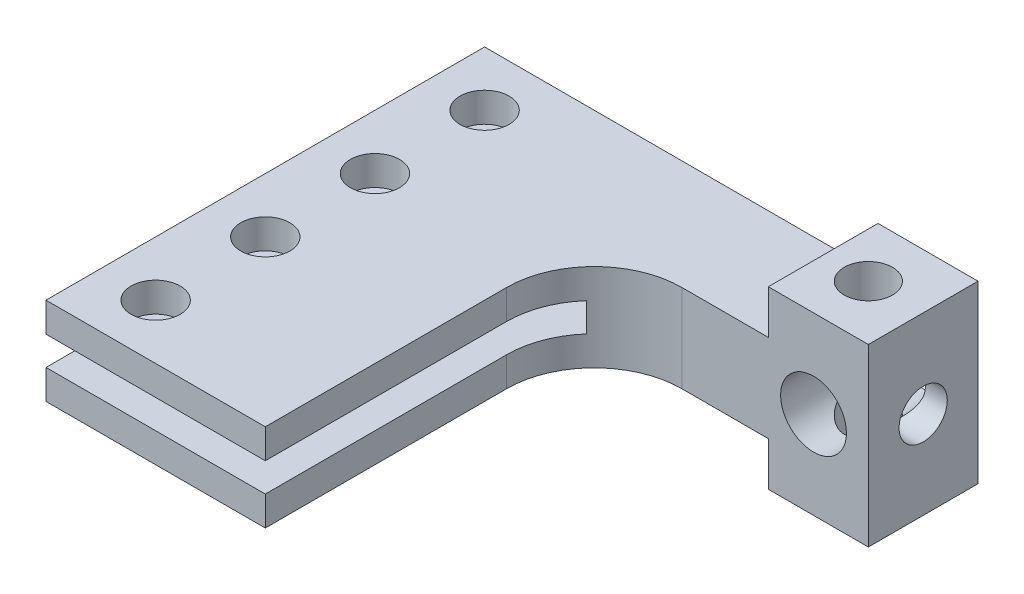
SolidWorks part; units mm, degrees
ref_plane "Front Plane" through (0, 0, 0) normal (0, 0, 1) x (1, 0, 0)
ref_plane "Top Plane" through (0, 0, 0) normal (0, 1, 0) x (1, 0, 0)
ref_plane "Right Plane" through (0, 0, 0) normal (1, 0, 0) x (0, 0, -1)
sketch "Sketch1" plane through (0, 0, 0) normal (0, 1, 0) x (1, 0, 0)
  line L0 (-33.097, 5.3879) -> (-20.397, 5.3879)
  line L2 (-20.397, 5.3879) -> (-4.522, 5.3879)
  line L3 (-4.522, 5.3879) -> (-4.522, -0.9621)
  line L4 (-4.522, -0.9621) -> (-20.397, -0.9621)
  line L5 (-20.397, -0.9621) -> (-20.397, -20.0121)
  line L6 (-20.397, -20.0121) -> (-33.097, -20.0121)
  line L7 (-33.097, -20.0121) -> (-33.097, 5.3879)
  dimension "D1" = 25.4
  dimension "D2" = 12.7
  dimension "D3" = 6.35
  dimension "D4" = 15.875
extrude "Boss-Extrude1" add sketch "Sketch1" along normal blind 5.08
sketch "Sketch2" plane through (-33.097, 0, 0) normal (-1, 0, 0) x (0, 0, 1)
  line L0 (-5.3879, 5.08) -> (-5.3879, 0) construction
  line L1 (-5.3879, 3.3735) -> (20.0121, 3.3735)
  line L2 (-5.3879, 3.3735) -> (-5.3879, 1.7065)
  line L3 (-5.3879, 1.7065) -> (20.0121, 1.7065)
  line L4 (20.0121, 3.3735) -> (20.0121, 1.7065)
  line L5 (20.0121, 5.08) -> (20.0121, 0) construction
  line L6 (7.3121, 5.08) -> (7.3121, 3.3735) construction
  line L7 (-5.3879, 5.08) -> (20.0121, 5.08) construction
  line L8 (7.3121, 1.7065) -> (7.3121, 0) construction
  line L9 (-5.3879, 0) -> (20.0121, 0) construction
  dimension "D1" = 1.6669
extrude "Cut-Extrude1" cut sketch "Sketch2" against normal blind 13.97
sketch "Sketch3" plane through (0, 5.08, 0) normal (0, 1, 0) x (1, 0, 0)
  line L0 (-33.097, 5.3879) -> (-33.097, -20.0121) construction
  line L2 (-33.097, -20.0121) -> (-20.397, -20.0121) construction
  circle A0 centre (-29.922, -16.8371) radius 1.4224
  circle A1 centre (-29.922, -10.4871) radius 1.4224
  circle A2 centre (-29.922, -4.1371) radius 1.4224
  circle A3 centre (-29.922, 2.2129) radius 1.4224
  dimension "D1" = 2.8448
  dimension "D4" = 4
  dimension "D2" = 3.175
  dimension "D3" = 3.175
  dimension "D5" = 6.35
extrude "Cut-Extrude2" cut sketch "Sketch3" against normal blind 12.7
sketch "Sketch8" plane through (0, 5.08, 0) normal (0, 1, 0) x (1, 0, 0)
  line L0 (-20.397, -0.9621) -> (-4.522, -0.9621) construction
  line L1 (-4.522, 5.3879) -> (-10.3146, 5.3879)
  line L2 (-4.522, 5.3879) -> (-4.522, -0.9621)
  line L3 (-4.522, -0.9621) -> (-10.3146, -0.9621)
  line L4 (-10.3146, 5.3879) -> (-10.3146, -0.9621)
extrude "Boss-Extrude2" add sketch "Sketch8" along normal blind 2.54 and the other way blind 7.62
sketch "Sketch5" plane through (0, 0, 0.9621) normal (0, 0, 1) x (1, 0, 0)
  line L2 (-9.602, 2.54) -> (-9.602, 5.4864) construction
  circle A1 centre (-7.697, 2.54) radius 1.905
  dimension "D1" = 3.81
extrude "Cut-Extrude3" cut sketch "Sketch5" against normal blind 12.7
fillet "Fillet3" radius 5.08 2 edges at (-20.397, 4.2267, 0.9621) (-20.397, 0.8533, 0.9621)
sketch "Sketch7" plane through (0, 5.08, 0) normal (0, 1, 0) x (1, 0, 0)
  line L0 (-7.697, -0.9621) -> (-7.697, 5.3879) construction
  line L2 (-10.3146, 5.3879) -> (-33.097, 5.3879) construction
  circle A0 centre (-7.697, 2.2129) radius 1.397
  dimension "D1" = 2.794
extrude "Cut-Extrude5" cut sketch "Sketch7" against normal through all and the other way through all contours A0
sketch "Sketch6" plane through (-4.522, 0, 0) normal (1, 0, 0) x (0, 0, -1)
  line L0 (2.2129, 5.08) -> (2.2129, 0) construction
  line L1 (3.6353, 5.08) -> (0.7905, 5.08) construction
  line L2 (-0.9621, 0) -> (5.3879, 0) construction
  circle A0 centre (2.2129, 2.54) radius 1.397
  point P9 (2.2129, 2.54)
  dimension "D1" = 2.794
extrude "Cut-Extrude4" cut sketch "Sketch6" against normal up to next
equation "\"bolt_hole\"= .112in'holes for screws"
